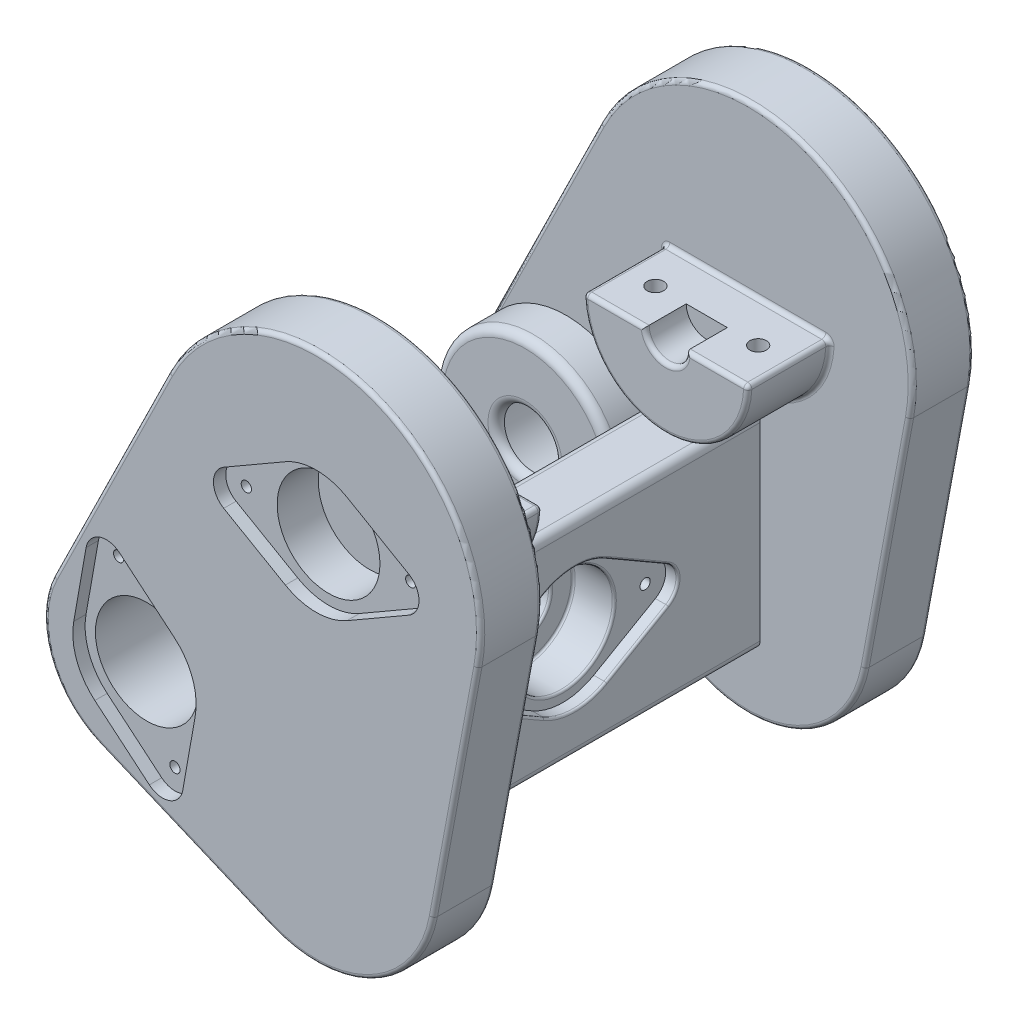
SolidWorks part; units mm, degrees
other "Markup1"
sketch "Sketch17" plane through (40, 40, -60) normal (0.6706, 0.1026, -0.7347) x (-0.7381, -0.0065, -0.6746)
ref_plane "Front Plane" through (0, 0, 0) normal (0, 0, 1) x (1, 0, 0)
ref_plane "Top Plane" through (0, 0, 0) normal (0, 1, 0) x (1, 0, 0)
ref_plane "Right Plane" through (0, 0, 0) normal (1, 0, 0) x (0, 0, -1)
ref_plane "Plane1" through (0, 0, 60) normal (0, 0, 1) x (1, 0, 0)
sketch "Sketch2" plane through (0, 0, 60) normal (0, 0, 1) x (1, 0, 0)
  line L2 (0, -60) -> (0, 0) construction
  line L3 (-39.322, -7.3333) -> (-28.5085, -65.3167)
  line L4 (39.322, -7.3333) -> (28.5085, -65.3167)
  circle A0 centre (0, 0) radius 30 construction
  arc A1 (39.322, -7.3333) -> (-39.322, -7.3333) centre (0, 0) ccw
  circle A2 centre (0, -60) radius 24 construction
  arc A3 (-28.5085, -65.3167) -> (28.5085, -65.3167) centre (0, -60) ccw
  circle A4 centre (0, 0) radius 12.5
  circle A5 centre (0, -60) radius 12.5 construction
  dimension "D1" = 60
  dimension "D2" = 10
  dimension "D5" = 48
  dimension "D6" = 5
  dimension "D7" = 25
  dimension "D8" = 25
  dimension "D3" = 60
extrude "Boss-Extrude1" add sketch "Sketch2" against normal blind 15
sketch "Sketch13" plane through (0, 0, 45) normal (0, 0, -1) x (-1, 0, 0)
  line L0 (0, 0) -> (0, -60) construction
  line L2 (13, -74) -> (-3, -74)
  line L3 (13, -74) -> (13, -24)
  line L4 (13, -24) -> (-3, -24)
  line L5 (-3, -74) -> (-3, -24)
  line L6 (13, -74) -> (-3, -24) construction
  line L7 (13, -24) -> (-3, -74) construction
  point P9 (5, -49)
  dimension "D1" = 16
  dimension "D2" = 50
  dimension "D3" = 11
  dimension "D4" = 5
extrude "Boss-Extrude5" add sketch "Sketch13" along normal up to surface (45 mm away) up to plane "Front Plane"
mirror "Mirror2" about plane through (0, 0, 0) normal (0, 0, 1) of "Boss-Extrude1", "Boss-Extrude5"
mirror "Mirror4" about plane through (0, 0, 0) normal (0, 0, 1) of "Boss-Extrude1"
sketch "Sketch5" plane through (0, 0, 0) normal (0, 0, 1) x (1, 0, 0)
  point P0 (0, 0)
sketch "Sketch14" plane through (3, 0, 0) normal (1, 0, 0) x (0, 0, -1)
  line L0 (45, -24) -> (-45, -24) construction
  circle A0 centre (0, -49) radius 12.5
  dimension "D1" = 25
  dimension "D2" = 25
extrude "Cut-Extrude1" cut sketch "Sketch14" against normal blind 13
sketch "Sketch15" plane through (3, 0, 0) normal (1, 0, 0) x (0, 0, -1)
  line L0 (-22.5, -44.6699) -> (-7.5, -36.0096)
  line L1 (7.5, -36.0096) -> (22.5, -44.6699)
  line L2 (-22.5, -53.3301) -> (-7.5, -61.9904)
  line L3 (7.5, -61.9904) -> (22.5, -53.3301)
  arc A0 (-7.5, -61.9904) -> (7.5, -61.9904) centre (0, -49) ccw
  circle A1 centre (20, -49) radius 1.25
  circle A2 centre (-20, -49) radius 1.25
  arc A3 (-22.5, -44.6699) -> (-22.5, -53.3301) centre (-20, -49) ccw
  arc A4 (22.5, -53.3301) -> (22.5, -44.6699) centre (20, -49) ccw
  arc A5 (7.5, -36.0096) -> (-7.5, -36.0096) centre (0, -49) ccw
  dimension "D1" = 30
  dimension "D2" = 2.5
  dimension "D3" = 20
  dimension "D4" = 20
extrude "Cut-Extrude2" cut sketch "Sketch15" against normal blind 3
sketch "Sketch16" plane through (3, 0, 0) normal (1, 0, 0) x (0, 0, -1)
  circle A0 centre (0, -49) radius 7
  circle A5 centre (20, -49) radius 1.25 construction
  circle A6 centre (-20, -49) radius 1.25 construction
  circle A7 centre (20, -49) radius 1.25
  circle A8 centre (-20, -49) radius 1.25
  dimension "D3" = 14
extrude "Cut-Extrude3" cut sketch "Sketch16" against normal through all
fillet "Fillet3" radius 0.5 3 edges at (-10, -49, -7) (0, -49, -12.5) (-10, -49, -12.5)
fillet "Fillet4" radius 0.5 1 edges at (-13, -49, -7)
fillet "Fillet5" radius 0.5 8 edges at (3, -34, 0) (3, -40.3397, -15) (3, -49, -25) (3, -57.6603, -15) (3, -64, 0) (3, -57.6603, 15) (3, -49, 25) (3, -40.3397, 15)
sketch "Sketch18" plane through (0, 0, 0) normal (0, 0, 1) x (1, 0, 0)
  line L0 (0, 0) -> (0, -49) construction
  line L1 (0, -49) -> (60, -49) construction
  line L2 (60, -49) -> (0, 0) construction
  dimension "D1" = 49
  dimension "D2" = 60
sketch "Sketch21" plane through (0, 0, 45) normal (0, 0, -1) x (-1, 0, 0)
  line L0 (0, 0) -> (0, -49) construction
  line L1 (0, -49) -> (-44.2154, -49) construction
  line L2 (-44.2154, -49) -> (0, 0) construction
  line L5 (-63.9491, -39.2748) -> (-35.8795, 17.6822)
  line L6 (-52.7436, -69.2798) -> (-11.2417, -86.7324)
  line L7 (-39.322, -7.3333) -> (-28.5085, -65.3167)
  line L8 (39.322, -7.3333) -> (32.1833, -45.612)
  line L9 (52.7436, -69.2798) -> (11.2417, -86.7324)
  line L10 (63.9491, -39.2748) -> (35.8795, 17.6822)
  line L11 (31.7709, -47.8233) -> (28.5085, -65.3167)
  line L12 (35.8795, 17.6822) -> (11.2417, -86.7324)
  circle A0 centre (0, 0) radius 44 construction
  arc A1 (-63.9491, -39.2748) -> (-52.7436, -69.2798) centre (-44.2154, -49) ccw
  arc A2 (-28.5085, -65.3167) -> (28.5085, -65.3167) centre (0, -60) ccw construction
  arc A3 (39.322, -7.3333) -> (-39.322, -7.3333) centre (0, 0) ccw construction
  arc A4 (-11.2417, -86.7324) -> (28.5085, -65.3167) centre (0, -60) ccw
  arc A5 (39.322, -7.3333) -> (-35.8795, 17.6822) centre (0, 0) ccw
  arc A6 (-35.8795, 17.6822) -> (-39.322, -7.3333) centre (0, 0) ccw
  arc A7 (-11.2417, -86.7324) -> (-28.5085, -65.3167) centre (0, -60) cw
  circle A8 centre (-44.2154, -49) radius 12.5
  arc A9 (11.2417, -86.7324) -> (28.5085, -65.3167) centre (0, -60) ccw
  arc A10 (35.8795, 17.6822) -> (39.322, -7.3333) centre (0, 0) cw
  arc A11 (63.9491, -39.2748) -> (52.7436, -69.2798) centre (44.2154, -49) cw
  circle A12 centre (44.2154, -49) radius 12.5
  arc M4 (39.322, -7.3333) -> (-39.322, -7.3333) centre (0, 0) ccw
  arc M6 (-28.5085, -65.3167) -> (28.5085, -65.3167) centre (0, -60) ccw
  line M7 (28.5085, -65.3167) -> (39.322, -7.3333)
  dimension "D2" = 88
  dimension "D3" = 44
  dimension "D4" = 25
  dimension "D1" = 66
extrude "Boss-Extrude7" add sketch "Sketch21" against normal blind 15 contours A12 L9 A11 L10 M7 M6 M4 | A12 L12 M7 M4 M6
sketch "Sketch23" plane through (0, 0, 45) normal (0, 0, -1) x (-1, 0, 0)
  arc A1 (52.7436, -69.2798) -> (63.9491, -39.2748) centre (44.2154, -49) ccw construction
  circle A4 centre (44.2154, -49) radius 12.5
  circle A5 centre (44.2154, -49) radius 22
  dimension "D2" = 25
extrude "Boss-Extrude8" add sketch "Sketch23" along normal blind 10
sketch "Sketch24" plane through (0, 0, 35) normal (0, 0, -1) x (-1, 0, 0)
  circle A0 centre (44.2154, -49) radius 12.5
extrude "Cut-Extrude4" cut sketch "Sketch24" against normal through all
sketch "Sketch25" plane through (0, 0, 35) normal (0, 0, -1) x (-1, 0, 0)
  circle A0 centre (44.2154, -49) radius 12.5
  circle A1 centre (44.2154, -49) radius 7
  dimension "D1" = 14
  dimension "D2" = 25
extrude "Boss-Extrude9" add sketch "Sketch25" against normal blind 2
sketch "Sketch26" plane through (0, 0, 60) normal (0, 0, 1) x (1, 0, 0)
  line L0 (-51.0558, -30.2061) -> (-37.375, -67.7939) construction
  line L1 (-44.2154, -49) -> (-29.2154, -49) construction
  line L2 (-34.5736, -37.5093) -> (-47.8418, -26.3759)
  line L3 (-55.9798, -29.3379) -> (-58.9875, -46.3953)
  line L4 (-29.4433, -51.6047) -> (-32.4509, -68.6621)
  line L5 (-53.8572, -60.4907) -> (-40.5889, -71.6241)
  arc A0 (-58.9875, -46.3953) -> (-53.8572, -60.4907) centre (-44.2154, -49) ccw
  arc A1 (-40.5889, -71.6241) -> (-32.4509, -68.6621) centre (-37.375, -67.7939) ccw
  arc A2 (-47.8418, -26.3759) -> (-55.9798, -29.3379) centre (-51.0558, -30.2061) ccw
  arc A3 (-29.4433, -51.6047) -> (-34.5736, -37.5093) centre (-44.2154, -49) ccw
  point P5 (-44.2154, -49)
  dimension "D1" = 30
  dimension "D2" = 40
  dimension "D3" = 110
extrude "Cut-Extrude5" cut sketch "Sketch26" against normal blind 3
sketch "Sketch27" plane through (0, 0, 57) normal (0, 0, 1) x (1, 0, 0)
  circle A0 centre (-51.0558, -30.2061) radius 1.25
  circle A1 centre (-37.375, -67.7939) radius 1.25
  dimension "D1" = 2.5
  dimension "D2" = 2.5
extrude "Cut-Extrude6" cut sketch "Sketch27" against normal blind 8
mirror "Mirror12" about plane through (0, 0, 0) normal (0, 0, 1) of "Cut-Extrude6", "Boss-Extrude9", "Cut-Extrude5", "Cut-Extrude4", "Boss-Extrude8", "Boss-Extrude7"
sketch "Sketch28" plane through (0, 0, 45) normal (0, 0, -1) x (-1, 0, 0)
  circle A0 centre (0, 0) radius 20
  dimension "D1" = 40
extrude "Boss-Extrude10" add sketch "Sketch28" against normal blind 2
sketch "Sketch29" plane through (0, 0, 45) normal (0, 0, -1) x (-1, 0, 0)
  line L0 (-20, 0) -> (20, 0)
  arc A0 (-20, 0) -> (20, 0) centre (0, 0) ccw
  dimension "D1" = 40
extrude "Boss-Extrude11" add sketch "Sketch29" along normal blind 20
sketch "Sketch30" plane through (0, 0, 25) normal (0, 0, -1) x (-1, 0, 0)
  line L0 (20, 0) -> (-20, 0) construction
  circle A0 centre (0, 0) radius 5
  dimension "D1" = 10
extrude "Cut-Extrude7" cut sketch "Sketch30" against normal blind 10
sketch "Sketch31" plane through (0, 0, 0) normal (0, 1, 0) x (1, 0, 0)
  line L0 (-20, -25) -> (-5, -25) construction
  line L1 (-12.5, -25) -> (12.5, -25)
  line L2 (-12.5, -25) -> (-12.5, -35) construction
  line L3 (-12.5, -35) -> (12.5, -35) construction
  line L4 (12.5, -25) -> (12.5, -35) construction
  line L6 (5, -25) -> (20, -25) construction
  line L8 (5, -35) -> (-5, -35) construction
  circle A0 centre (12.5, -35) radius 2
  circle A1 centre (-12.5, -35) radius 2
  point P8 (12.5, -25)
  dimension "D2" = 4
  dimension "D3" = 4
extrude "Cut-Extrude8" cut sketch "Sketch31" against normal blind 12 contours A1 | A0
sketch "Sketch32" plane through (-30.9224, 58.3079, 60) normal (0, 0, 1) x (0.342, 0.9397, 0)
  line L0 (-51.0558, -30.2061) -> (-37.375, -67.7939) construction
  line L1 (-44.2154, -49) -> (-29.2154, -49) construction
  line L2 (-34.5736, -37.5093) -> (-47.8418, -26.3759)
  line L3 (-55.9798, -29.3379) -> (-58.9875, -46.3953)
  line L4 (-29.4433, -51.6047) -> (-32.4509, -68.6621)
  line L5 (-53.8572, -60.4907) -> (-40.5889, -71.6241)
  line L6 (-90.2603, -65.759) -> (-69.7391, -122.1405) construction
  arc A0 (-58.9875, -46.3953) -> (-53.8572, -60.4907) centre (-44.2154, -49) ccw
  arc A1 (-40.5889, -71.6241) -> (-32.4509, -68.6621) centre (-37.375, -67.7939) ccw
  arc A2 (-47.8418, -26.3759) -> (-55.9798, -29.3379) centre (-51.0558, -30.2061) ccw
  arc A3 (-29.4433, -51.6047) -> (-34.5736, -37.5093) centre (-44.2154, -49) ccw
  circle A4 centre (-44.2154, -49) radius 12.5 construction
extrude "Cut-Extrude9" cut sketch "Sketch32" against normal blind 3
sketch "Sketch33" plane through (0, 0, 57) normal (0, 0, 1) x (1, 0, 0)
  circle A0 centre (20, 0) radius 1.25
  circle A1 centre (-20, 0) radius 1.25
  dimension "D1" = 2.5
extrude "Cut-Extrude10" cut sketch "Sketch33" against normal blind 8
mirror "Mirror13" about plane through (0, 0, 0) normal (0, 0, 1) of "Boss-Extrude11", "Cut-Extrude7", "Cut-Extrude8", "Cut-Extrude9", "Cut-Extrude10", "Boss-Extrude10"
fillet "Fillet6" radius 1 22 edges at (-31.9927, -78.0061, -45) (-31.9927, -78.0061, -60) (13.7548, -85.5305, -45) (-49.9143, -10.7963, -45) (-49.9143, -10.7963, -60) (12.6256, 37.9551, -45) (13.7548, -85.5305, -60) (-64.8251, -56.6968, -60) (12.6256, 37.9551, -60) (-31.9927, -78.0061, 45) (-31.9927, -78.0061, 60) (13.7548, -85.5305, 45) (-49.9143, -10.7963, 45) (-49.9143, -10.7963, 60) (12.6256, 37.9551, 45) (13.7548, -85.5305, 60) (-64.8251, -56.6968, 60) (12.6256, 37.9551, 60) (33.9153, -36.325, -45) (33.9153, -36.325, -60) (33.9153, -36.325, 45) (33.9153, -36.325, 60)
fillet "Fillet7" radius 1 16 edges at (20, 0, -35) (0, 0, -45) (-20, 0, -35) (0, 0, 45) (0, -20, -25) (0, -20, -45) (-20, 0, 35) (20, 0, 35) (0, -20, 25) (0, -20, 45) (0, -5, -25) (0, -5, 25) (12.5, 0, 25) (-12.5, 0, 25) (-12.5, 0, -25) (12.5, 0, -25)
fillet "Fillet8" radius 2 4 edges at (-13, -74, 0) (3, -74, 0) (-13, -24, 0) (3, -24, 0)
fillet "Fillet9" radius 2 4 edges at (-51.2154, -49, -35) (-66.2154, -49, -35) (-51.2154, -49, 35) (-66.2154, -49, 35)
